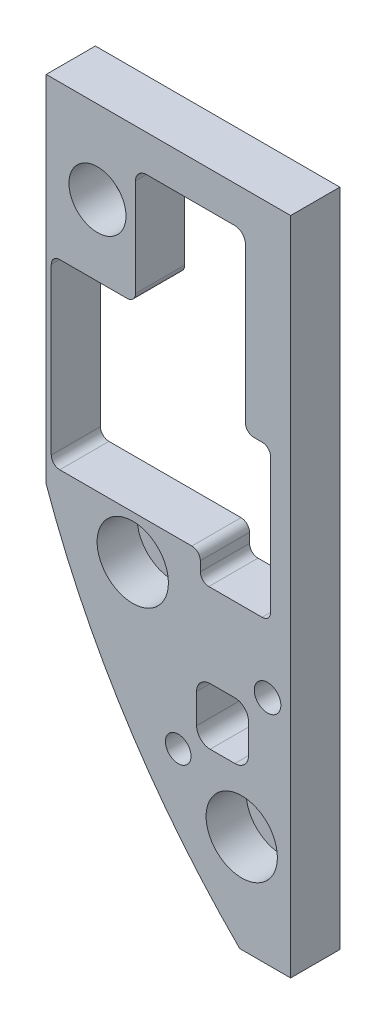
SolidWorks part; units mm, degrees
material "PET"
ref_plane "Front" through (0, 0, 0) normal (0, 0, 1) x (1, 0, 0)
ref_plane "Top" through (0, 0, 0) normal (0, 1, 0) x (1, 0, 0)
ref_plane "Right" through (0, 0, 0) normal (1, 0, 0) x (0, 0, -1)
sketch "Sketch1" plane through (0, 0, 0) normal (0, 0, 1) x (1, 0, 0)
  line L4 (0, -17.78) -> (-45.72, -17.78)
  line L5 (-45.72, -17.78) -> (-45.72, -84.1375)
  line L6 (-9.525, -141.2875) -> (0, -141.2875)
  line L7 (0, -141.2875) -> (0, -17.78)
  line L8 (0, -17.78) -> (-45.72, -17.78)
  line L9 (-45.72, -17.78) -> (-45.72, -84.1375)
  line L10 (-9.525, -141.2875) -> (0, -141.2875)
  line L11 (0, -141.2875) -> (0, -17.78)
  line L17 (-30.5943, -46.5015) -> (-43.1857, -46.5015)
  line L18 (-44.7732, -48.089) -> (-44.7732, -78.9652)
  line L19 (-43.1857, -80.5527) -> (-18.4742, -80.5527)
  line L20 (-16.8867, -82.1402) -> (-16.8867, -83.9371)
  line L21 (-15.2992, -85.5246) -> (-5.3275, -85.5246)
  line L22 (-3.74, -83.9371) -> (-3.74, -58.7502)
  line L23 (-6.8707, -57.1627) -> (-5.3275, -57.1627)
  line L80 (-8.4582, -55.1307) -> (-8.4582, -26.6573)
  line L81 (-26.9748, -57.1627) -> (-10.4902, -57.1627)
  line L82 (-29.0068, -26.6573) -> (-29.0068, -55.1307)
  line L83 (-10.4902, -24.6253) -> (-26.9748, -24.6253)
  line L84 (-8.4582, -55.5752) -> (-8.4582, -26.6573)
  line L86 (-29.0068, -26.6573) -> (-29.0068, -44.914)
  line L87 (-10.4902, -24.6253) -> (-26.9748, -24.6253)
  circle A1 centre (-36.1315, -33.274) radius 2.1526
  circle A2 centre (-36.1315, -33.274) radius 2.1527
  circle A5 centre (-9.144, -122.9995) radius 2.1526
  circle A6 centre (-9.144, -122.9995) radius 2.1527
  arc A7 (-45.72, -84.1375) -> (-9.525, -141.2875) centre (97.9169, -33.2042) ccw
  arc A8 (-45.72, -84.1375) -> (-9.525, -141.2875) centre (97.9169, -33.2042) ccw
  arc A9 (-3.74, -58.7502) -> (-5.3275, -57.1627) centre (-5.3275, -58.7502) ccw
  arc A10 (-8.4582, -55.5752) -> (-6.8707, -57.1627) centre (-6.8707, -55.5752) ccw
  arc A11 (-30.5943, -46.5015) -> (-29.0068, -44.914) centre (-30.5943, -44.914) ccw
  arc A12 (-43.1857, -46.5015) -> (-44.7732, -48.089) centre (-43.1857, -48.089) ccw
  arc A13 (-44.7732, -78.9652) -> (-43.1857, -80.5527) centre (-43.1857, -78.9652) ccw
  arc A14 (-18.4742, -80.5527) -> (-16.8867, -82.1402) centre (-18.4742, -82.1402) cw
  arc A15 (-16.8867, -83.9371) -> (-15.2992, -85.5246) centre (-15.2992, -83.9371) ccw
  arc A16 (-8.4582, -26.6573) -> (-10.4902, -24.6253) centre (-10.4902, -26.6573) ccw
  arc A17 (-10.4902, -57.1627) -> (-8.4582, -55.1307) centre (-10.4902, -55.1307) ccw
  arc A18 (-29.0068, -55.1307) -> (-26.9748, -57.1627) centre (-26.9748, -55.1307) ccw
  arc A19 (-26.9748, -24.6253) -> (-29.0068, -26.6573) centre (-26.9748, -26.6573) ccw
  arc A20 (-8.4582, -26.6573) -> (-10.4902, -24.6253) centre (-10.4902, -26.6573) ccw
  arc A23 (-26.9748, -24.6253) -> (-29.0068, -26.6573) centre (-26.9748, -26.6573) ccw
  arc A24 (-5.3275, -85.5246) -> (-3.74, -83.9371) centre (-5.3275, -83.9371) ccw
  circle A25 centre (-4.3174, -98.0359) radius 2.487
  circle A26 centre (-21.0247, -114.6804) radius 2.3945
  dimension "D5" = 1.5875
  dimension "D1" = 0
  dimension "D3" = 0
  dimension "D4" = 0
  dimension "D9" = 1.27
extrude "Boss-Extrude1" add sketch "Sketch1" along normal blind 10.8
sketch "Sketch3" plane through (0, 0, 10.8) normal (0, 0, 1) x (1, 0, 0)
  circle A0 centre (-9.144, -122.9995) radius 6.6675
  circle A1 centre (-29.5275, -88.7095) radius 6.6675
  circle A3 centre (-36.1315, -33.274) radius 5.334
  dimension "D1" = 10.668
  dimension "D2" = 13.335
  dimension "D3" = 13.335
extrude "Cut-Extrude1" cut sketch "Sketch3" against normal blind 7.5
sketch "Sketch4" plane through (0, 0, 0) normal (0, 0, -1) x (-1, 0, 0)
  line L4 (0, -17.78) -> (0, -141.2875)
  line L5 (0, -141.2875) -> (9.525, -141.2875)
  line L6 (45.72, -84.1375) -> (45.72, -17.78)
  line L7 (45.72, -17.78) -> (0, -17.78)
  line L8 (0, -17.78) -> (0, -141.2875)
  line L9 (0, -141.2875) -> (9.525, -141.2875)
  line L10 (45.72, -84.1375) -> (45.72, -17.78)
  line L11 (45.72, -17.78) -> (0, -17.78)
  arc A1 (9.525, -141.2875) -> (45.72, -84.1375) centre (-97.9169, -33.2042) ccw
  arc A2 (9.525, -141.2875) -> (45.72, -84.1375) centre (-97.9169, -33.2042) ccw
  dimension "D1" = 0
extrude "Cut-Extrude2" cut sketch "Sketch4" against normal blind 1.6
sketch "Sketch5" plane through (0, 0, 10.8) normal (0, 0, 1) x (1, 0, 0)
  line L1 (-17.5902, -101.1208) -> (-7.8818, -101.1208)
  line L2 (-17.5902, -101.1208) -> (-17.5902, -111.7542)
  line L3 (-17.5902, -111.7542) -> (-7.8818, -111.7542)
  line L4 (-7.8818, -101.1208) -> (-7.8818, -111.7542)
  line L5 (-17.5902, -101.1208) -> (-7.8818, -111.7542) construction
  line L6 (-17.5902, -111.7542) -> (-7.8818, -101.1208) construction
  point P0 (-12.736, -106.4375)
extrude "Cut-Extrude3" cut sketch "Sketch5" against normal through all
fillet "Fillet1" radius 2.54 4 edges at (-7.8818, -101.1208, 6.2) (-17.5902, -101.1208, 6.2) (-17.5902, -111.7542, 6.2) (-7.8818, -111.7542, 6.2)
